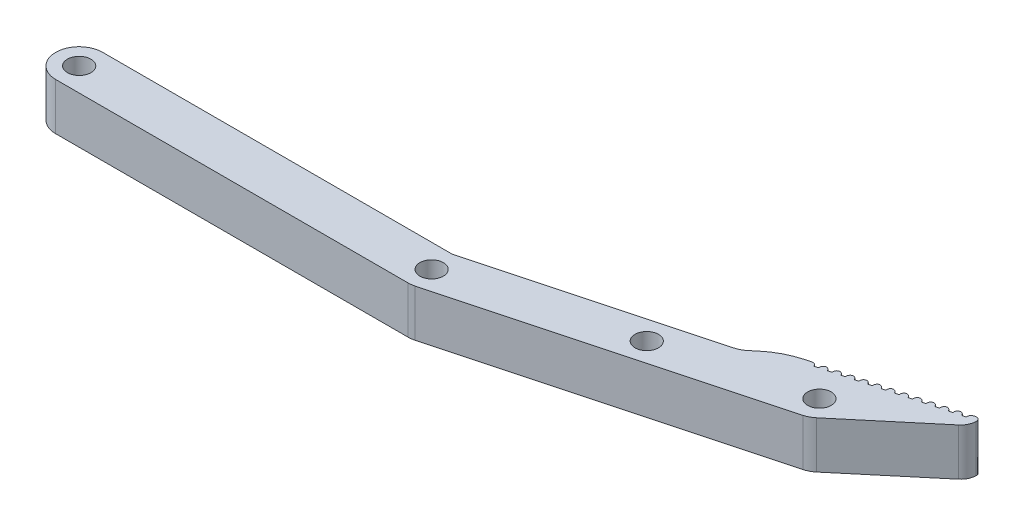
SolidWorks part; units mm, degrees
ref_plane "Front Plane" through (0, 0, 0) normal (0, 0, 1) x (1, 0, 0)
ref_plane "Top Plane" through (0, 0, 0) normal (0, 1, 0) x (1, 0, 0)
ref_plane "Right Plane" through (0, 0, 0) normal (1, 0, 0) x (0, 0, -1)
sketch "Sketch1" plane through (0, 0, 0) normal (0, 1, 0) x (1, 0, 0)
  line L0 (96.5113, 18.5981) -> (94.4702, 18.0511)
  line L3 (85.9751, 8.1644) -> (95.8285, 16.4324)
  line L4 (44.605, 3) -> (72.9936, 10.6067)
  line L5 (78.736, 13.8352) -> (96.5113, 18.5981)
  line L6 (0, 3) -> (44.605, 3)
  line L7 (45, -3) -> (0, -3)
  line L8 (45.7765, -2.8978) -> (84.8232, 7.5648)
  line L9 (74.8963, 11.8364) -> (74.1455, 11.2063)
  circle A0 centre (0, 0) radius 1.5
  circle A2 centre (45, 0) radius 1.5
  circle A6 centre (0, 0) radius 3
  circle A7 centre (45, 0) radius 3
  circle A8 centre (84.0467, 10.4625) radius 1.5
  circle A9 centre (84.0467, 10.4625) radius 3
  arc A10 (95.8285, 16.4324) -> (96.5113, 18.5981) centre (94.4702, 18.0511) ccw
  arc A11 (74.8963, 11.8364) -> (78.736, 13.8352) centre (81.3242, 4.1759) cw
  arc A12 (74.1455, 11.2063) -> (72.9936, 10.6067) centre (72.2171, 13.5045) cw
  circle A14 centre (66.66, 5.8038) radius 1.5
  dimension "D1" = 10
  dimension "D2" = 3
extrude "Boss-Extrude1" add sketch "Sketch1" along normal blind 6 contours L9 A12 L4 L6 A6 L7 A7 L8 A9 L3 A10 L0 L5 A11 | A6 A0 | A7 A2 | A9 A8 region at (95.5417, 0, -17.7133) region at (85.3928, 0, -7.8768) region at (45.3805, 0, 2.8902) region at (-2.9151, 0, 0)
sketch "Sketch2" plane through (1.8155, 0, 6.7756) normal (-0.2588, 0, -0.9659) x (-0.9659, 0, 0.2588)
  line L2 (-98.0363, 0) -> (-79.6339, 0) construction
  line L3 (-80.9173, 6) -> (-81.4173, 6)
  line L4 (-80.9173, 6) -> (-80.9173, 0)
  line L5 (-80.9173, 0) -> (-81.4173, 0)
  line L6 (-81.4173, 6) -> (-81.4173, 0)
  line L7 (-80.9173, 6) -> (-81.4173, 0) construction
  line L8 (-80.9173, 0) -> (-81.4173, 6) construction
  line L9 (-82.3173, 6) -> (-82.3173, 0)
  line L10 (-82.3173, 6) -> (-82.8173, 6)
  line L11 (-82.8173, 6) -> (-82.8173, 0)
  line L12 (-82.3173, 0) -> (-82.8173, 0)
  line L13 (-83.7173, 6) -> (-83.7173, 0)
  line L14 (-83.7173, 6) -> (-84.2173, 6)
  line L15 (-84.2173, 6) -> (-84.2173, 0)
  line L16 (-83.7173, 0) -> (-84.2173, 0)
  line L17 (-85.1173, 6) -> (-85.1173, 0)
  line L18 (-85.1173, 6) -> (-85.6173, 6)
  line L19 (-85.6173, 6) -> (-85.6173, 0)
  line L20 (-85.1173, 0) -> (-85.6173, 0)
  line L21 (-86.5173, 6) -> (-86.5173, 0)
  line L22 (-86.5173, 6) -> (-87.0173, 6)
  line L23 (-87.0173, 6) -> (-87.0173, 0)
  line L24 (-86.5173, 0) -> (-87.0173, 0)
  line L25 (-87.9173, 6) -> (-87.9173, 0)
  line L26 (-87.9173, 6) -> (-88.4173, 6)
  line L27 (-88.4173, 6) -> (-88.4173, 0)
  line L28 (-87.9173, 0) -> (-88.4173, 0)
  line L29 (-89.3173, 6) -> (-89.3173, 0)
  line L30 (-89.3173, 6) -> (-89.8173, 6)
  line L31 (-89.8173, 6) -> (-89.8173, 0)
  line L32 (-89.3173, 0) -> (-89.8173, 0)
  line L33 (-90.7173, 6) -> (-90.7173, 0)
  line L34 (-90.7173, 6) -> (-91.2173, 6)
  line L35 (-91.2173, 6) -> (-91.2173, 0)
  line L36 (-90.7173, 0) -> (-91.2173, 0)
  line L37 (-92.1173, 6) -> (-92.1173, 0)
  line L38 (-92.1173, 6) -> (-92.6173, 6)
  line L39 (-92.6173, 6) -> (-92.6173, 0)
  line L40 (-92.1173, 0) -> (-92.6173, 0)
  line L41 (-93.5173, 6) -> (-93.5173, 0)
  line L42 (-93.5173, 6) -> (-94.0173, 6)
  line L43 (-94.0173, 6) -> (-94.0173, 0)
  line L44 (-93.5173, 0) -> (-94.0173, 0)
  line L45 (-94.9173, 6) -> (-94.9173, 0)
  line L46 (-94.9173, 6) -> (-95.4173, 6)
  line L47 (-95.4173, 6) -> (-95.4173, 0)
  line L48 (-94.9173, 0) -> (-95.4173, 0)
  line L49 (-96.3173, 6) -> (-96.3173, 0)
  line L50 (-96.3173, 6) -> (-96.8173, 6)
  line L51 (-96.8173, 6) -> (-96.8173, 0)
  line L52 (-96.3173, 0) -> (-96.8173, 0)
  dimension "D1" = 12
extrude "Cut-Extrude1" cut sketch "Sketch2" against normal blind 0.5
fillet "Fillet1" radius 0.5 25 edges at (96.5113, 3, -18.5981) (95.3338, 3, -18.2825) (94.8509, 3, -18.1531) (93.9815, 3, -17.9202) (93.4986, 3, -17.7908) (92.6292, 3, -17.5578) (92.1463, 3, -17.4284) (91.2769, 3, -17.1955) (90.794, 3, -17.0661) (89.9246, 3, -16.8332) (89.4417, 3, -16.7037) (88.5723, 3, -16.4708) (88.0894, 3, -16.3414) (87.2201, 3, -16.1085) (86.7371, 3, -15.9791) (85.8678, 3, -15.7461) (85.3848, 3, -15.6167) (84.5155, 3, -15.3838) (84.0325, 3, -15.2544) (83.1632, 3, -15.0214) (82.6802, 3, -14.892) (81.8109, 3, -14.6591) (81.3279, 3, -14.5297) (80.4586, 3, -14.2967) (79.9756, 3, -14.1673)
